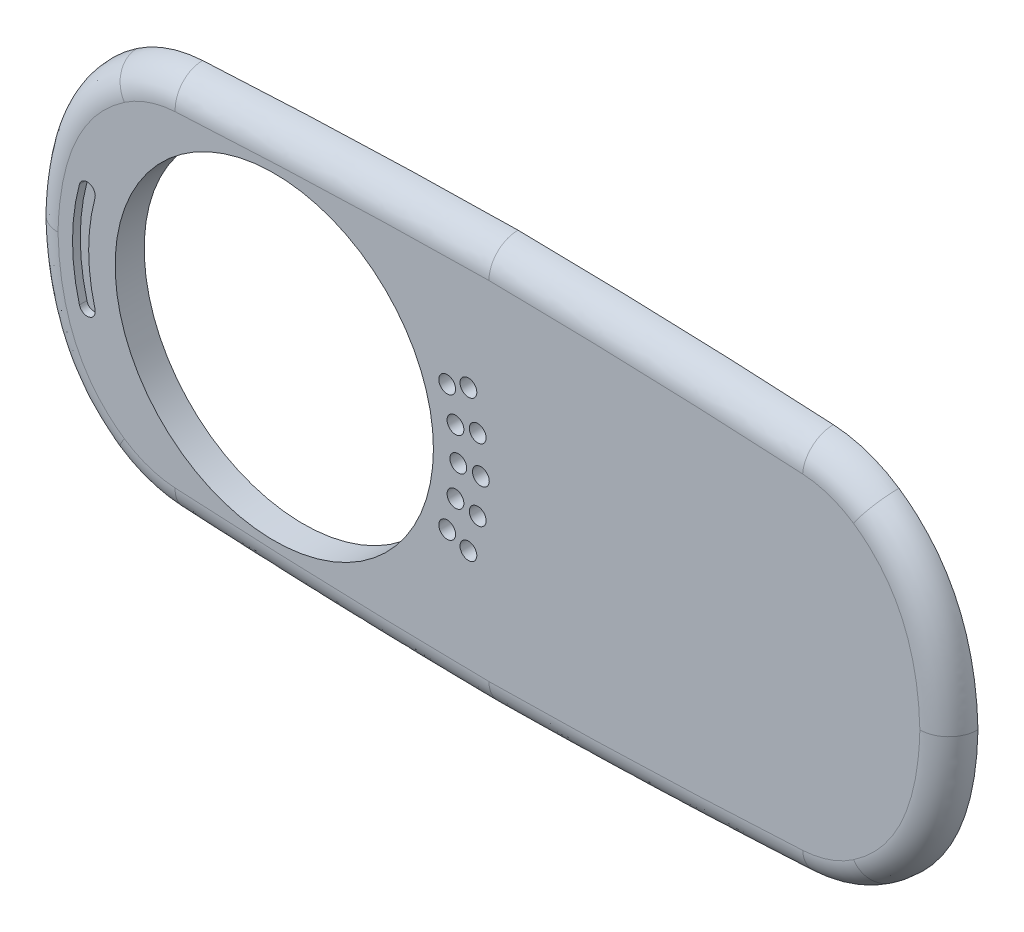
SolidWorks part; units mm, degrees
ref_plane "Front Plane" through (0, 0, 0) normal (0, 0, 1) x (1, 0, 0)
ref_plane "Top Plane" through (0, 0, 0) normal (0, 1, 0) x (1, 0, 0)
ref_plane "Right Plane" through (0, 0, 0) normal (1, 0, 0) x (0, 0, -1)
sketch "Sketch1" plane through (0, 0, 0) normal (0, 0, 1) x (1, 0, 0)
  line L0 (-35.625, 0) -> (35.625, 0) construction
  line L1 (0, 15.7) -> (0, -15.7) construction
  arc A0 (24.4235, -14.8674) -> (29.5009, -13.1395) centre (23.8586, -4.8833) ccw
  arc A1 (24.4235, 14.8674) -> (29.5009, 13.1395) centre (23.8586, 4.8833) cw
  arc A2 (-24.4235, 14.8674) -> (-29.5009, 13.1395) centre (-23.8586, 4.8833) ccw
  arc A3 (-24.4235, -14.8674) -> (-29.5009, -13.1395) centre (-23.8586, -4.8833) cw
  circle A4 centre (-16.625, 0) radius 12.325
  spline S0 degree 3 poles (0, 15.7) (8.1473, 15.6052) (16.2888, 15.3276) (24.4235, 14.8674) knots 0 0 0 0 0.923945 0.923945 0.923945 0.923945
  spline S1 degree 3 poles (29.5009, 13.1395) (29.7988, 12.9359) (33.5991, 10.1134) (35.4967, 5.6063) (35.625, 0) knots 0.189061 0.189061 0.189061 0.189061 0.250305 1 1 1 1
  spline S2 degree 3 poles (0, -15.7) (8.1473, -15.6052) (16.2888, -15.3276) (24.4235, -14.8674) knots 0 0 0 0 0.923945 0.923945 0.923945 0.923945
  spline S3 degree 3 poles (29.5009, -13.1395) (29.7988, -12.9359) (33.5991, -10.1134) (35.4967, -5.6063) (35.625, 0) knots 0.189061 0.189061 0.189061 0.189061 0.250305 1 1 1 1
  spline S4 degree 3 poles (0, 15.7) (-8.1473, 15.6052) (-16.2888, 15.3276) (-24.4235, 14.8674) knots 0 0 0 0 0.923945 0.923945 0.923945 0.923945
  spline S5 degree 3 poles (-29.5009, 13.1395) (-29.7988, 12.9359) (-33.5991, 10.1134) (-35.4967, 5.6063) (-35.625, 0) knots 0.189061 0.189061 0.189061 0.189061 0.250305 1 1 1 1
  spline S6 degree 3 poles (-29.5009, -13.1395) (-29.7988, -12.9359) (-33.5991, -10.1134) (-35.4967, -5.6063) (-35.625, 0) knots 0.189061 0.189061 0.189061 0.189061 0.250305 1 1 1 1
  spline S7 degree 3 poles (0, -15.7) (-8.1473, -15.6052) (-16.2888, -15.3276) (-24.4235, -14.8674) knots 0 0 0 0 0.923945 0.923945 0.923945 0.923945
  point P8 (0, 0)
  dimension "D6" = 10
  dimension "D7" = 24.65
  dimension "D1" = 71.25
  dimension "D2" = 31.4
  dimension "D3" = 15.4
  dimension "D4" = 19
  dimension "D5" = 12.5
extrude "Boss-Extrude1" add sketch "Sketch1" against normal blind 2.25
fillet "Fillet1" radius 2.25 12 edges at (27.0802, 14.3502, 0) (-27.0802, 14.3502, 0) (27.0802, -14.3502, 0) (-27.0802, -14.3502, 0)
sketch "Sketch2" plane through (0, 0, 0) normal (0, 0, 1) x (1, 0, 0)
  line L0 (-16.625, 12.325) -> (-16.625, -12.325) construction
  line L1 (-16.625, 0) -> (-31.625, 0) construction
  line L2 (-16.625, 0) -> (-31.1139, 3.8823) construction
  line L3 (-16.625, 0) -> (-31.1139, -3.8823) construction
  circle A0 centre (-16.625, 0) radius 12.325 construction
  arc A1 (-31.1139, 3.8823) -> (-31.1139, -3.8823) centre (-16.625, 0) ccw construction
  arc A2 (-31.7176, 4.044) -> (-31.7176, -4.044) centre (-16.625, 0) ccw
  arc A3 (-30.5102, 3.7205) -> (-30.5102, -3.7205) centre (-16.625, 0) ccw
  arc A4 (-30.5102, 3.7205) -> (-31.7176, 4.044) centre (-31.1139, 3.8823) ccw
  arc A5 (-31.7176, -4.044) -> (-30.5102, -3.7205) centre (-31.1139, -3.8823) ccw
  dimension "D1" = 15
  dimension "D2" = 15
  dimension "D3" = 0.625
extrude "Cut-Extrude1" cut sketch "Sketch2" against normal blind 1.5
sketch "Sketch3" plane through (0, 0, -1.5) normal (0, 0, 1) x (1, 0, 0)
  arc A0 (-30.6068, 3.7464) -> (-31.621, 4.0182) centre (-31.1139, 3.8823) ccw
  arc A1 (-31.621, 4.0182) -> (-31.621, -4.0182) centre (-16.625, 0) ccw
  arc A2 (-31.621, -4.0182) -> (-30.6068, -3.7464) centre (-31.1139, -3.8823) ccw
  arc A3 (-30.6068, 3.7464) -> (-30.6068, -3.7464) centre (-16.625, 0) ccw
  arc A4 (-30.5102, 3.7205) -> (-31.7176, 4.044) centre (-31.1139, 3.8823) ccw
  arc A5 (-31.7176, 4.044) -> (-31.7176, -4.044) centre (-16.625, 0) ccw
  arc A6 (-31.7176, -4.044) -> (-30.5102, -3.7205) centre (-31.1139, -3.8823) ccw
  arc A7 (-30.5102, 3.7205) -> (-30.5102, -3.7205) centre (-16.625, 0) ccw
  arc A8 (-30.5102, 3.7205) -> (-31.7176, 4.044) centre (-31.1139, 3.8823) ccw construction
  arc A9 (-31.7176, 4.044) -> (-31.7176, -4.044) centre (-16.625, 0) ccw construction
  arc A10 (-31.7176, -4.044) -> (-30.5102, -3.7205) centre (-31.1139, -3.8823) ccw construction
  arc A11 (-30.5102, 3.7205) -> (-30.5102, -3.7205) centre (-16.625, 0) ccw construction
  dimension "D1" = 0
  dimension "D2" = 0.1
extrude "Boss-Extrude3" add sketch "Sketch3" along normal blind 1 separate body
sketch "Sketch4" plane through (0, 0, 0) normal (0, 0, 1) x (1, 0, 0)
  line L0 (-16.625, 0) -> (-2.375, 0) construction
  line L1 (-2.375, 0) -> (-0.625, 0) construction
  line L2 (-16.625, 0) -> (-3.2344, 4.8738) construction
  line L3 (-16.625, 0) -> (-3.2344, -4.8738) construction
  line L4 (-16.625, 0) -> (-0.8681, 2.7784) construction
  line L5 (-16.625, 0) -> (-0.8681, -2.7784) construction
  arc A0 (-3.2344, -4.8738) -> (-3.2344, 4.8738) centre (-16.625, 0) ccw construction
  arc A1 (-1.5899, -5.4723) -> (-1.5899, 5.4723) centre (-16.625, 0) ccw construction
  circle A2 centre (-3.2344, 4.8738) radius 0.65
  circle A3 centre (-2.5915, 2.4745) radius 0.65
  circle A4 centre (-0.8681, 2.7784) radius 0.65
  circle A5 centre (-1.5899, 5.4723) radius 0.65
  circle A6 centre (-2.375, 0) radius 0.65
  circle A7 centre (-0.625, 0) radius 0.65
  circle A8 centre (-1.5899, -5.4723) radius 0.65
  circle A9 centre (-3.2344, -4.8738) radius 0.65
  circle A10 centre (-0.8681, -2.7784) radius 0.65
  circle A11 centre (-2.5915, -2.4745) radius 0.65
  dimension "D6" = 1.3
  dimension "D1" = 14.25
  dimension "D2" = 16
  dimension "D3" = 20
  dimension "D5" = 10
  dimension "D4" = 1.75
extrude "Cut-Extrude2" cut sketch "Sketch4" against normal up to surface (2.25 mm away) up to face at (-4.3, 0, -2.25)
